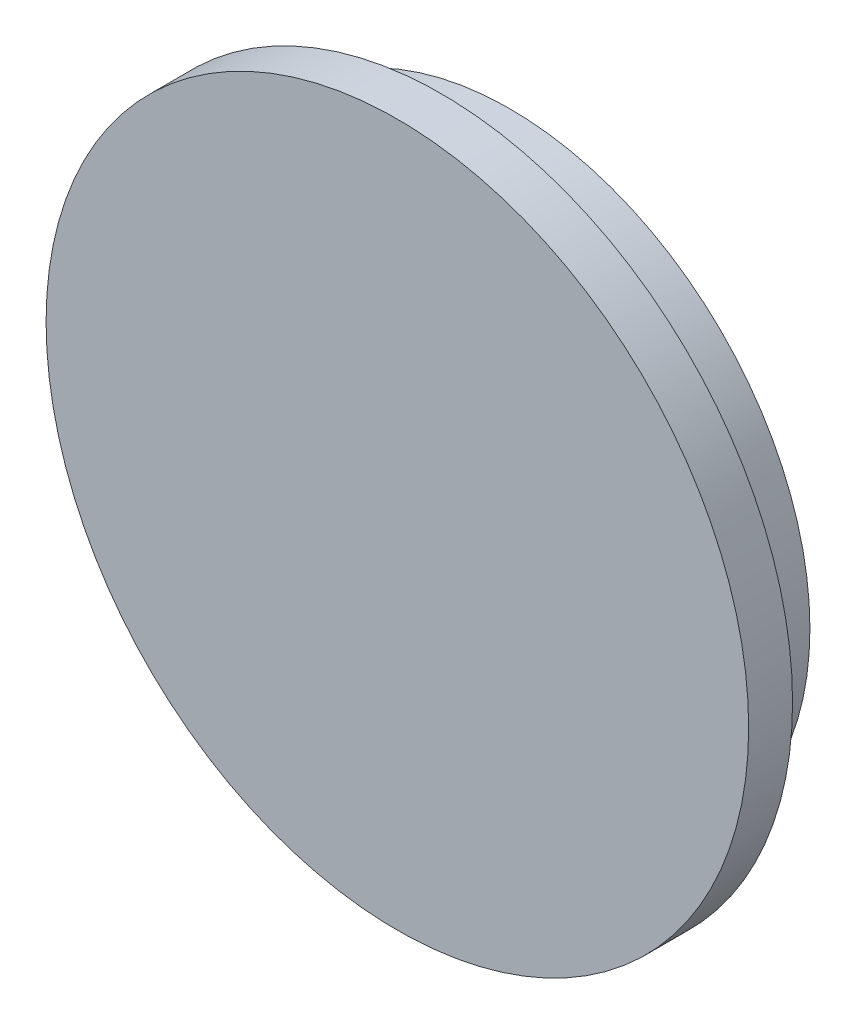
SolidWorks part; units mm, degrees
ref_plane "Płaszczyzna przednia" through (0, 0, 0) normal (0, 0, 1) x (1, 0, 0)
ref_plane "Płaszczyzna górna" through (0, 0, 0) normal (0, 1, 0) x (1, 0, 0)
ref_plane "Płaszczyzna prawa" through (0, 0, 0) normal (1, 0, 0) x (0, 0, -1)
sketch "Szkic1" plane through (0, 0, 0) normal (0, 0, 1) x (1, 0, 0)
  circle A0 centre (0, 0) radius 12
  circle A1 centre (0.343, 0.4765) radius 10.25
  dimension "D1" = 24
  dimension "D2" = 20.5
extrude "Dodanie-wyciągnięcie1" add sketch "Szkic1" along normal blind 1.5 contours A1 | A0 A1 region at (-11.6606, 0, 0) region at (0.343, 0.4765, 0)
extrude "Dodanie-wyciągnięcie2" add sketch "Szkic1<3>" against normal blind 2 contours A1 region at (0.343, 0.4765, 0)
sketch "Szkic1<3>" plane through (0, 0, 0) normal (0, 0, 1) x (1, 0, 0) same geometry as "Szkic1"
